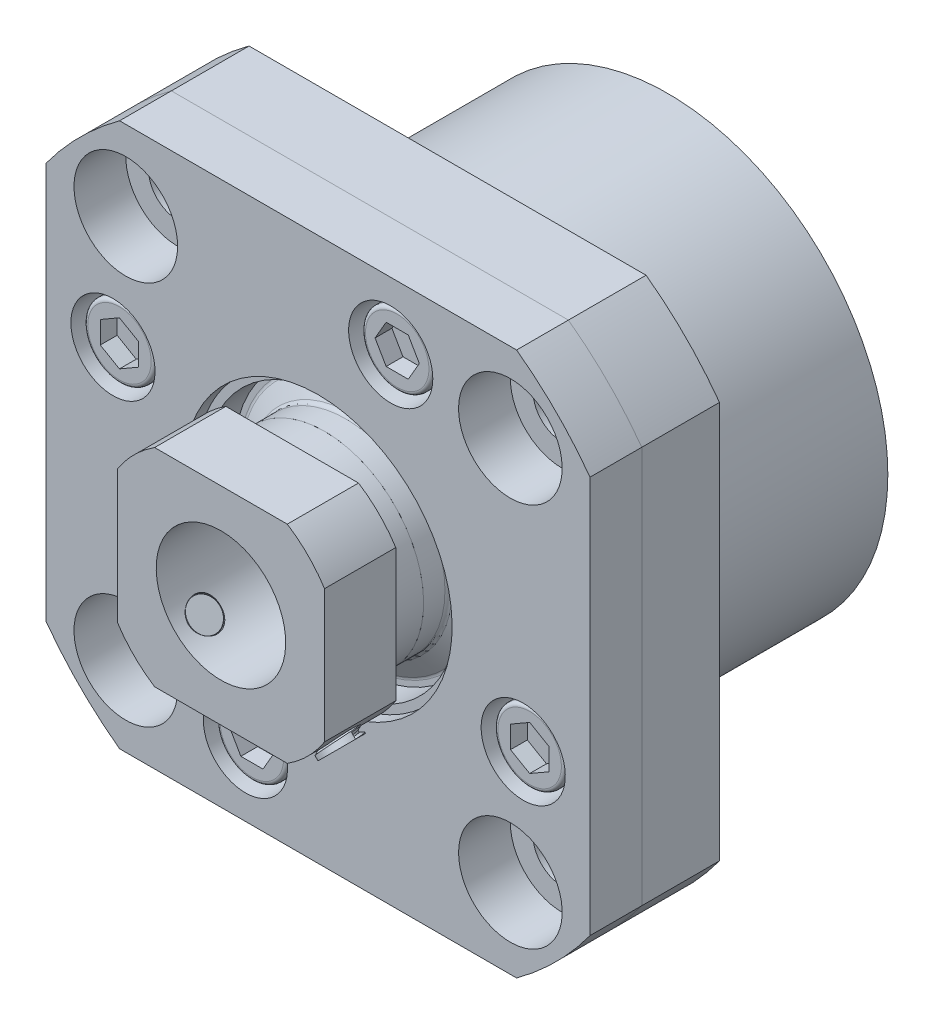
SolidWorks part; units mm, degrees
material "6063-T5"
ref_plane "Ebene vorne" through (0, 0, 0) normal (0, 0, 1) x (1, 0, 0)
ref_plane "Ebene oben" through (0, 0, 0) normal (0, 1, 0) x (1, 0, 0)
ref_plane "Ebene rechts" through (0, 0, 0) normal (1, 0, 0) x (0, 0, -1)
sketch "Skizze1" plane through (0, 0, 0) normal (1, 0, 0) x (0, 0, -1)
  line L0 (0, 0) -> (23, 0) construction
  line L1 (23, 10.35) -> (2, 10.35)
  line L2 (2, 10.35) -> (2, 13)
  line L3 (2, 13) -> (0, 13)
  line L4 (0, 13) -> (0, 26)
  line L5 (0, 26) -> (6, 26)
  line L6 (6, 26) -> (6, 17)
  line L7 (6, 17) -> (23, 17)
  line L8 (23, 17) -> (23, 10.35)
  dimension "D1" = 23
  dimension "D2" = 10.35
  dimension "D3" = 13
  dimension "D4" = 17
  dimension "D5" = 26
  dimension "D6" = 17
  dimension "D7" = 2
revolve "Rotation1" add sketch "Skizze1" angle 360 about L0
sketch "Skizze2" plane through (0, 0, 0) normal (1, 0, 0) x (0, 0, -1)
  line L0 (0, 0) -> (-4, 0) construction
  line L1 (2, 10.35) -> (-4, 10.35)
  line L2 (-4, 10.35) -> (-4, 26)
  line L3 (-4, 26) -> (0, 26)
  line L4 (0, 26) -> (0, 13)
  line L5 (0, 13) -> (2, 13)
  line L6 (2, 13) -> (2, 10.35)
  dimension "D1" = 2
  dimension "D2" = 10.35
  dimension "D3" = 4
  dimension "D4" = 13
  dimension "D5" = 26
revolve "Rotation2" add sketch "Skizze2" angle 360 about L0
sketch "Skizze3" plane through (0, 0, 4) normal (0, 0, 1) x (1, 0, 0)
  line L1 (-21, 21) -> (21, 21)
  line L2 (-21, 21) -> (-21, -21)
  line L3 (-21, -21) -> (21, -21)
  line L4 (21, 21) -> (21, -21)
  line L5 (-21, 21) -> (21, -21) construction
  line L6 (-21, -21) -> (21, 21) construction
  point P0 (0, 0)
  dimension "D1" = 42
  dimension "D2" = 42
extrude "Schnitt-Linear austragen1" cut sketch "Skizze3" against normal through all flip side to cut
sketch "Skizze4" plane through (0, 0, 0) normal (1, 0, 0) x (0, 0, -1)
  line L0 (-3.5, 0) -> (23.5, 0) construction
  line L1 (10, 0) -> (10, 10.35) construction
  line L2 (23.5, 5) -> (-3.5, 5)
  line L3 (23.5, 5) -> (23.5, 7.65)
  line L4 (23.5, 7.65) -> (21.62, 7.65)
  line L5 (21.62, 7.65) -> (20.73, 9.2)
  line L6 (20.73, 9.2) -> (20.73, 9.72)
  line L7 (20.73, 9.72) -> (23, 9.72)
  line L8 (23, 9.72) -> (23, 10.35)
  line L9 (23, -10.35) -> (23, 10.35) construction
  line L10 (23, 10.35) -> (-3, 10.35)
  line L11 (-3, 9.72) -> (-3, 10.35)
  line L12 (-0.73, 9.72) -> (-3, 9.72)
  line L13 (-0.73, 9.2) -> (-0.73, 9.72)
  line L14 (-1.62, 7.65) -> (-0.73, 9.2)
  line L15 (-3.5, 7.65) -> (-1.62, 7.65)
  line L16 (-3.5, 5) -> (-3.5, 7.65)
  point P24 (10, 5)
  dimension "D1" = 3.5
  dimension "D2" = 23.5
  dimension "D3" = 5
  dimension "D4" = 7.65
  dimension "D5" = 1.88
  dimension "D6" = 0.89
  dimension "D7" = 1.55
  dimension "D8" = 0.52
revolve "Rotation3" add sketch "Skizze4" angle 360 about L0
fillet "Verrundung1" radius 0.4 4 edges at (9.2, 0, 0.73) (7.65, 0, 1.62) (9.72, 0, -20.73) (9.2, 0, -20.73)
sketch "Skizze5" plane through (0, 0, 0) normal (1, 0, 0) x (0, 0, -1)
  line L0 (-3.5, 5) -> (-3.5, 7.65)
  line L1 (-3.5, 7.65) -> (-6, 7.65)
  line L2 (-3.5, 5) -> (-11.5, 5)
  line L3 (-11.5, 5) -> (-11.5, 9.5)
  line L4 (-11.5, 9.5) -> (-6, 9.5)
  line L5 (-6, 9.5) -> (-6, 7.65)
  line L6 (-3.5, 0) -> (-11.5, 0) construction
  dimension "D1" = 8
  dimension "D2" = 2.5
  dimension "D3" = 9.5
revolve "Rotation4" add sketch "Skizze5" angle 360 about L6
sketch "Skizze6" plane through (0, 0, 11.5) normal (0, 0, 1) x (1, 0, 0)
  line L1 (-8, -8) -> (8, -8)
  line L2 (-8, -8) -> (-8, 8)
  line L3 (-8, 8) -> (8, 8)
  line L4 (8, -8) -> (8, 8)
  line L5 (-8, -8) -> (8, 8) construction
  line L6 (-8, 8) -> (8, -8) construction
  point P0 (0, 0)
  dimension "D1" = 16
  dimension "D2" = 16
extrude "Schnitt-Linear austragen2" cut sketch "Skizze6" against normal up to surface (5.5 mm away) flip side to cut up to face at (0, 9.5, 6)
hole_wizard "Stirnsenkung für M4 Flachkopfschraube mit Schlitz1" positions "Skizze8" profile "Skizze7" counterbore size "M4" standard "ISO" end condition through all
sketch "Skizze8" plane through (0, 0, 4) normal (0, 0, 1) x (1, 0, 0)
  line L0 (0, 0) -> (-18.3848, 18.3848) construction
  arc A0 (-15.3297, 21) -> (-21, 15.3297) centre (0, 0) ccw construction
  point P0 (-14.8492, 14.8492)
  dimension "D1" = 21
sketch "Skizze7" plane through (-14.8492, 14.8492, 4) normal (1, 0, 0) x (0, -1, 0)
  line L0 (0, 0) -> (0, 27.5)
  line L1 (0, 27.5) -> (2.25, 27.5)
  line L3 (2.25, 27.5) -> (2.25, 4)
  line L4 (2.25, 4) -> (4, 4)
  line L5 (4, 4) -> (4, 0)
  line L7 (4, 0) -> (0, 0)
  line L11 (0, -6.35) -> (0, 107.95) construction
  dimension "Bohrerdurchmesser" = 4.5
  dimension "Bohrungstiefe" = 27.5
  dimension "Senkdurchmesser2" = 8
  dimension "Senktiefe2" = 4
pattern_circular "Kreismuster1" count 4 over 360 about axis through (0, 0, 3.5) along (0, 0, 1) of "Stirnsenkung für M4 Flachkopfschraube mit Schlitz1" reverse direction yes
hole_wizard "Stirnsenkung für M3 Zylinderschraube mit Innensechskant1" positions "Skizze10" profile "Skizze9" counterbore size "M3" standard "ISO"
sketch "Skizze10" plane through (0, 0, 4) normal (0, 0, 1) x (1, 0, 0)
  point P0 (5.61, 15.84)
  dimension "D1" = 15.84
  dimension "D2" = 5.61
sketch "Skizze9" plane through (5.61, 15.84, 4) normal (1, 0, 0) x (0, -1, 0)
  line L0 (0, 0) -> (0, 10.0215)
  line L1 (0, 10.0215) -> (1.7, 9)
  line L2 (1.7, 9) -> (1.7, 3)
  line L3 (1.7, 3) -> (3.25, 3)
  line L4 (3.25, 3) -> (3.25, 0)
  line L5 (3.25, 0) -> (0, 0)
  line L10 (0, 10.0215) -> (-1.7, 9) construction
  line L11 (0, -6.35) -> (0, 107.95) construction
  dimension "Bohrerdurchmesser" = 3.4
  dimension "Bohrungstiefe" = 9
  dimension "Senkdurchmesser2" = 6.5
  dimension "Senktiefe2" = 3
  dimension "Spitzenwinkel" = 118
pattern_circular "Kreismuster2" count 4 over 360 about axis through (0, 0, 3.5) along (0, 0, 1) of "Stirnsenkung für M3 Zylinderschraube mit Innensechskant1"
ref_plane "Ebene1" through (0, 0, 0) normal (-0.7071, 0.7071, 0) x (0.7071, 0.7071, 0)
hole_wizard "M3 Gewindebohrung1" positions "Skizze13" profile "Skizze12" tap size "M3" standard "ISO" end condition through all
sketch "Skizze13" plane through (0, 0, 0) normal (-0.7071, 0.7071, 0) x (0.7071, 0.7071, 0)
  point P0 (0, -9.24)
  dimension "D1" = 9.24
sketch "Skizze12" plane through (0, 0, 9.24) normal (0, 0, 1) x (-0.7071, -0.7071, 0)
  line L0 (0, 0) -> (0, 11.3137)
  line L1 (0, 11.3137) -> (1.25, 11.3137)
  line L2 (1.25, 11.3137) -> (1.25, 0)
  line L5 (1.25, 0) -> (0, 0)
  line L11 (0, -6.35) -> (0, 107.95) construction
  dimension "Bohrerdurchmesser" = 2.5
  dimension "Bohrungstiefe" = 11.3137
cosmetic thread "Bohrungsgewinde2" parameters "D2"=3
mirror "Spiegeln1" about plane through (0, 0, 0) normal (1, 0, 0) of "M3 Gewindebohrung1"
sketch "Skizze14" plane through (0, 0, 4) normal (0, 0, 1) x (1, 0, 0)
  circle A0 centre (5.61, 15.84) radius 2.75
  dimension "D1" = 5.5
extrude "Aufsatz-Linear austragen1" add sketch "Skizze14" against normal up to surface (3 mm away) from offset 0.5 separate body contours A0 up to face at (7.31, 15.84, 1) offset against normal yes
sketch "Skizze15" plane through (0, 0, 3.5) normal (0, 0, 1) x (1, 0, 0)
  line L1 (6.4645, 14.36) -> (7.319, 15.84)
  line L2 (7.319, 15.84) -> (6.4645, 17.32)
  line L3 (6.4645, 17.32) -> (4.7555, 17.32)
  line L4 (4.7555, 17.32) -> (3.901, 15.84)
  line L5 (3.901, 15.84) -> (4.7555, 14.36)
  line L6 (4.7555, 14.36) -> (6.4645, 14.36)
  circle A0 centre (5.61, 15.84) radius 1.48 construction
  dimension "D1" = 1.48
extrude "Schnitt-Linear austragen3" cut sketch "Skizze15" against normal blind 1.3
fillet "Verrundung2" radius 0.3 1 edges at (8.36, 15.84, 3.5)
pattern_circular "Kreismuster4" count 4 over 360 about axis through (0, 0, 3.5) along (0, 0, 1) of bodies 121
sketch "Skizze16" plane through (0, 0, 0) normal (-0.7071, 0.7071, 0) x (0.7071, 0.7071, 0)
  circle A0 centre (0, -9.24) radius 1.5
  circle A1 centre (0, -9.24) radius 1.25 construction
  dimension "D1" = 3
extrude "Aufsatz-Linear austragen2" add sketch "Skizze16" against normal blind 5 from offset 5 separate body offset against normal yes
chamfer "Fase1" distance 0.3 angle 45 1 edges at (2.4749, -4.5962, 9.24)
thread "Gewinde1" pitch 0.5 method cut profile "Gewindeprofil1" start angle 0, offset 0, length 10, pitch 0.5, diameter 3
ref_plane "Ebene2" through (8.1317, -6.0104, 9.24) normal (0, 0, 1) x (0.7071, 0.7071, 0)
sketch "Gewindeprofil1" plane through (8.1317, -6.0104, 9.24) normal (0, 0, 1) x (0.7071, 0.7071, 0)
  line L0 (0, 0) -> (0, 0.5) construction
  line L11 (0, 0) -> (0, 0.4375)
  line L12 (0, 0.4375) -> (-0.2706, 0.2812)
  line L13 (-0.2706, 0.2812) -> (-0.2706, 0.1562)
  line L15 (-0.2706, 0.1562) -> (0, 0)
  line L17 (-0.2706, 0.2187) -> (0, 0.2187) construction
  point P2 (0, 0)
  dimension "Pitch" = 0.5
  dimension "Profile_Angle" = 60
  dimension "Profile_Land" = 0.125
  dimension "Profile_Height" = 0.2706
sketch "Skizze20" plane through (7.0711, -7.0711, 0) normal (0.7071, -0.7071, 0) x (0, 0, -1)
  line L1 (-8.805, -0.7534) -> (-8.37, 0)
  line L2 (-8.37, 0) -> (-8.805, 0.7534)
  line L3 (-8.805, 0.7534) -> (-9.675, 0.7534)
  line L4 (-9.675, 0.7534) -> (-10.11, 0)
  line L5 (-10.11, 0) -> (-9.675, -0.7534)
  line L6 (-9.675, -0.7534) -> (-8.805, -0.7534)
  circle A0 centre (-9.24, 0) radius 0.7534 construction
  dimension "D1" = 0.87
extrude "Schnitt-Linear austragen4" cut sketch "Skizze20" against normal blind 1.2
pattern_circular "Kreismuster6" count 2 over 270 about axis through (0, 0, 3.5) along (0, 0, 1) of bodies 127
